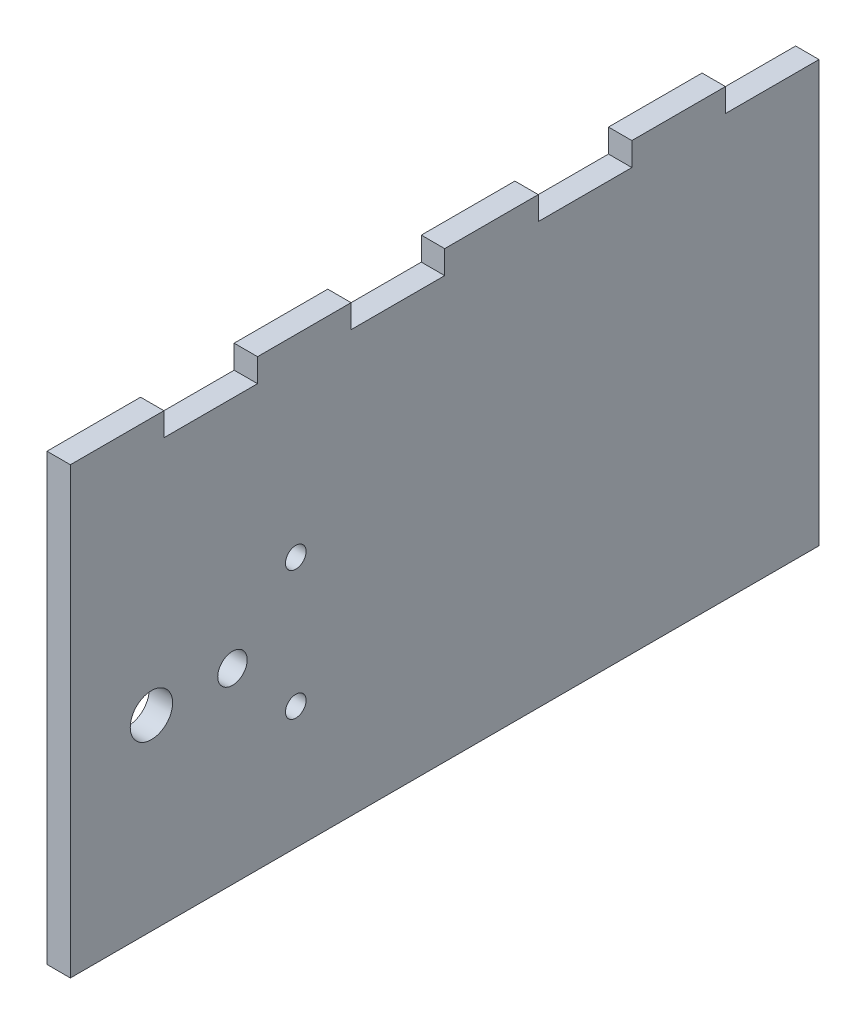
SolidWorks part; units mm, degrees
ref_plane "Front Plane" through (0, 0, 0) normal (0, 0, 1) x (1, 0, 0)
ref_plane "Top Plane" through (0, 0, 0) normal (0, 1, 0) x (1, 0, 0)
ref_plane "Right Plane" through (0, 0, 0) normal (1, 0, 0) x (0, 0, -1)
sketch "Sketch1" plane through (0, 0, 0) normal (1, 0, 0) x (0, 0, -1)
  line L0 (0, 0) -> (0, 60.325)
  line L1 (0, 60.325) -> (12.7, 60.325)
  line L2 (12.7, 57.15) -> (25.4, 57.15)
  line L3 (25.4, 57.15) -> (25.4, 60.325)
  line L4 (25.4, 60.325) -> (38.1, 60.325)
  line L5 (38.1, 60.325) -> (38.1, 57.15)
  line L6 (38.1, 57.15) -> (50.8, 57.15)
  line L7 (50.8, 57.15) -> (50.8, 60.325)
  line L8 (50.8, 60.325) -> (63.5, 60.325)
  line L9 (63.5, 60.325) -> (63.5, 57.15)
  line L10 (63.5, 57.15) -> (76.2, 57.15)
  line L11 (76.2, 57.15) -> (76.2, 60.325)
  line L12 (76.2, 60.325) -> (88.9, 60.325)
  line L13 (88.9, 60.325) -> (88.9, 57.15)
  line L14 (88.9, 57.15) -> (101.6, 57.15)
  line L15 (101.6, 57.15) -> (101.6, 0)
  line L16 (101.6, 0) -> (0, 0)
  line L17 (12.7, 60.325) -> (12.7, 57.15)
  dimension "D1" = 101.6
  dimension "D2" = 3.175
  dimension "D10" = 57.15
extrude "Boss-Extrude1" add sketch "Sketch1" along normal blind 3.175
sketch "Sketch2" plane through (3.175, 0, 0) normal (1, 0, 0) x (0, 0, -1)
  line L0 (11, 25.4) -> (30.591, 25.4) construction
  line L1 (0, 60.325) -> (0, 0) construction
  line L2 (50.8, 60.325) -> (50.8, 0) construction
  line L3 (0, 0) -> (101.6, 0) construction
  line L4 (30.591, 34.15) -> (30.591, 16.65) construction
  circle A4 centre (30.591, 16.65) radius 1.4
  circle A5 centre (30.591, 34.15) radius 1.4
  circle A6 centre (22, 25.4) radius 2
  circle A7 centre (11, 25.4) radius 2.877
  point P5 (-43.2868, 54.2473)
  dimension "D2" = 4
  dimension "D3" = 2.8
  dimension "D1" = 5.754
  dimension "D4" = 2.8
  dimension "D8" = 11
  dimension "D5" = 11
  dimension "D6" = 19.591
  dimension "D7" = 25.4
  dimension "D10" = 17.5
  dimension "D11" = 8.75
extrude "Cut-Extrude1" cut sketch "Sketch2" against normal up to next
